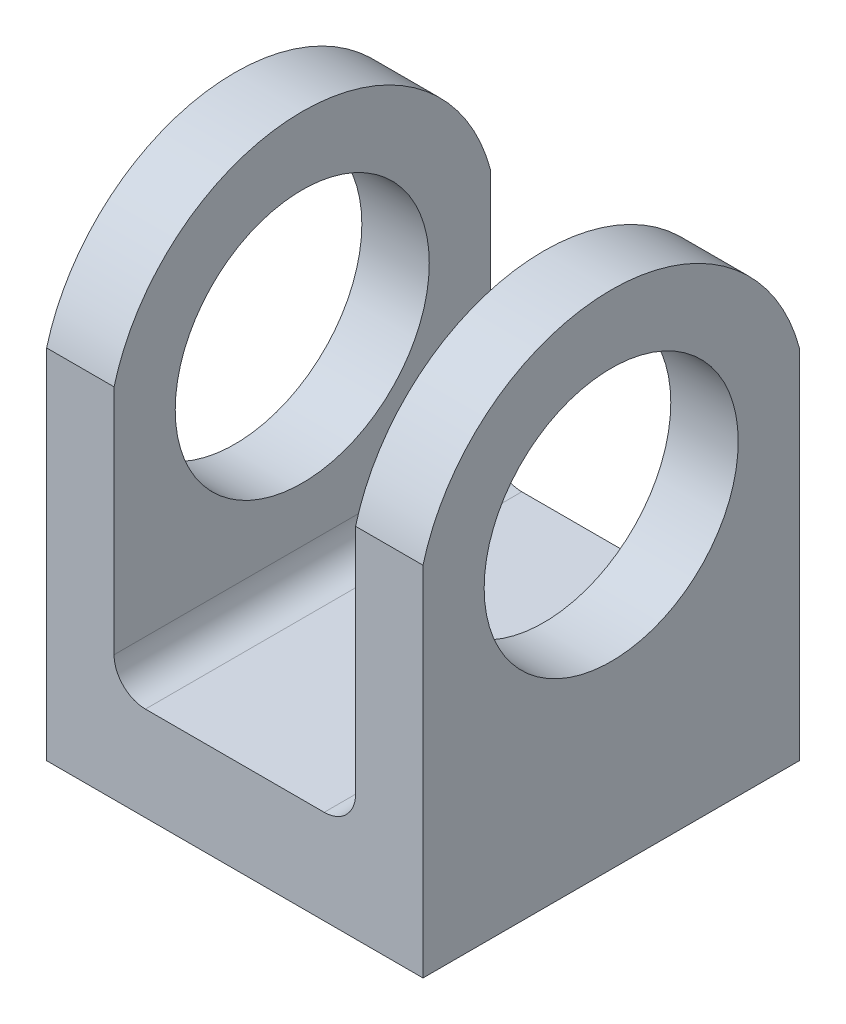
SolidWorks part; units mm, degrees
material "7075-O (SS)"
ref_plane "Front Plane" through (0, 0, 0) normal (0, 0, 1) x (1, 0, 0)
ref_plane "Top Plane" through (0, 0, 0) normal (0, 1, 0) x (1, 0, 0)
ref_plane "Right Plane" through (0, 0, 0) normal (1, 0, 0) x (0, 0, -1)
sketch "Sketch1" plane through (0, 0, 0) normal (0, 0, 1) x (1, 0, 0)
  line L1 (-60, -80) -> (60, -80)
  line L2 (-60, -80) -> (-60, 80)
  line L3 (-60, 80) -> (60, 80)
  line L4 (60, -80) -> (60, 80)
  line L5 (-60, -80) -> (60, 80) construction
  line L6 (-60, 80) -> (60, -80) construction
  point P0 (0, 0)
  dimension "D1" = 120
  dimension "D2" = 160
extrude "Boss-Extrude1" add sketch "Sketch1" along normal blind 120
sketch "Sketch2" plane through (0, 0, 120) normal (0, 0, 1) x (1, 0, 0)
  line L0 (60, 80) -> (-60, 80) construction
  line L1 (-38.5, -50) -> (38.5, -50)
  line L2 (-38.5, -50) -> (-38.5, 210)
  line L3 (-38.5, 210) -> (38.5, 210)
  line L4 (38.5, -50) -> (38.5, 210)
  line L5 (-38.5, -50) -> (38.5, 210) construction
  line L6 (-38.5, 210) -> (38.5, -50) construction
  line L7 (-60, -80) -> (60, -80) construction
  point P0 (0, 80)
  dimension "D1" = 77
  dimension "D2" = 30
extrude "Cut-Extrude1" cut sketch "Sketch2" against normal through all
sketch "Sketch3" plane through (-38.5, 0, 0) normal (1, 0, 0) x (0, 0, -1)
  line L0 (-60, 80) -> (-60, -50) construction
  line L1 (-120, 80) -> (0, 80) construction
  line L2 (0, -50) -> (-120, -50) construction
  circle A0 centre (-60, 17.8789) radius 40.5
  dimension "D1" = 81
extrude "Hinge Hole" cut sketch "Sketch3" against normal through all both and the other way through all
fillet "Fillet1" radius 10 2 edges at (38.5, -50, 60) (-38.5, -50, 60)
sketch "Sketch4" plane through (60, 0, 0) normal (1, 0, 0) x (0, 0, -1)
  line L1 (2.1211, 17.8789) -> (2.1211, 80)
  line L2 (2.1211, 80) -> (-122.1211, 80)
  line L3 (-122.1211, 80) -> (-122.1211, 17.8789)
  arc A0 (2.1211, 17.8789) -> (-122.1211, 17.8789) centre (-60, 17.8789) ccw
  line M2 (0, -80) -> (0, 80)
  line M3 (0, 80) -> (-120, 80)
  line M4 (-120, 80) -> (-120, -80)
extrude "Cut-Extrude2" cut sketch "Sketch4" against normal through all contours A0 M2 M3 | A0 L2 M4 region at (60, 67.9326, 106.2977) region at (60, 67.9326, 13.7023)
